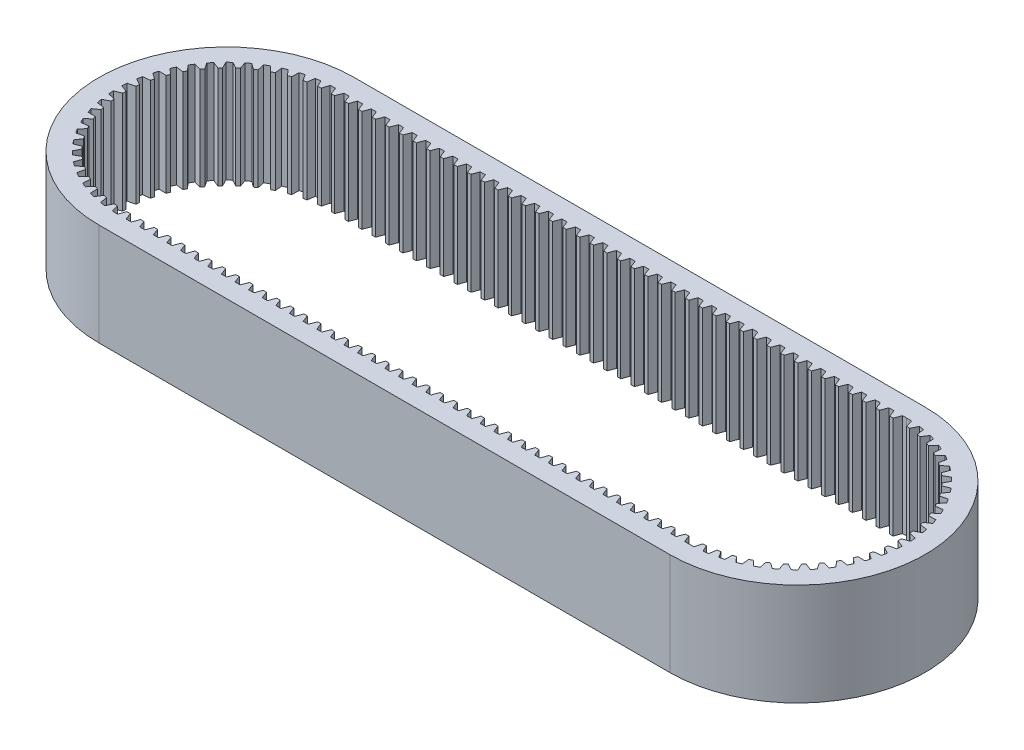
SolidWorks part; units mm, degrees
ref_plane "Front Plane" through (0, 0, 0) normal (0, 0, 1) x (1, 0, 0)
ref_plane "Top Plane" through (0, 0, 0) normal (0, 1, 0) x (1, 0, 0)
ref_plane "Right Plane" through (0, 0, 0) normal (1, 0, 0) x (0, 0, -1)
sketch "Sketch1" plane through (0, 0, 0) normal (0, 1, 0) x (1, 0, 0)
  line L0 (-16.765, 0) -> (16.765, 0) construction
  line L1 (-16.765, 6) -> (16.765, 6) construction
  line L2 (16.765, -6) -> (-16.765, -6) construction
  line L3 (16.765, -6.4) -> (-16.765, -6.4)
  line L4 (-16.765, 6.4) -> (16.765, 6.4)
  line L5 (16.765, -7.5) -> (-16.765, -7.5)
  line L6 (-16.765, 7.5) -> (16.765, 7.5)
  line L7 (-16.765, 6.4) -> (-16.615, 6)
  line L8 (-16.615, 6) -> (-16.415, 6)
  line L9 (-16.415, 6) -> (-16.265, 6.4)
  line L10 (-16.765, 6.4) -> (-16.265, 6.4)
  line L11 (-16.76, 6.3867) -> (-16.27, 6.3867) construction
  line L12 (-16.515, 6.3867) -> (-16.515, 6) construction
  arc A0 (-16.765, 6) -> (-16.765, -6) centre (-16.765, 0) ccw construction
  arc A1 (16.765, -6) -> (16.765, 6) centre (16.765, 0) ccw construction
  arc A2 (-16.765, 6.4) -> (-16.765, -6.4) centre (-16.765, 0) ccw
  arc A3 (16.765, -6.4) -> (16.765, 6.4) centre (16.765, 0) ccw
  arc A4 (-16.765, 7.5) -> (-16.765, -7.5) centre (-16.765, 0) ccw
  arc A5 (16.765, -7.5) -> (16.765, 7.5) centre (16.765, 0) ccw
  point P4 (0, 0)
  dimension "D2" = 12
  dimension "D3" = 12
  dimension "D1" = 33.53
  dimension "D6" = 33.53
  dimension "D7" = 0.5
  dimension "D8" = 0.2
  dimension "D9" = 0.0133
  dimension "D10" = 0.49
  dimension "D4" = 0.4
  dimension "D5" = 1.5
extrude "Boss-Extrude1" add sketch "Sketch1" along normal blind 6 contours L5 A5 L6 A4 A3 L3 A2 L4 region at (0, 0, 6.992)
extrude "Boss-Extrude2" add sketch "Sketch1<3>" along normal blind 6 contours L8 L9 L4 L7 region at (-16.515, 0, -6.2286)
sketch "Sketch1<3>" plane through (0, 0, 0) normal (0, 1, 0) x (1, 0, 0) same geometry as "Sketch1"
pattern_linear "LPattern1" count 42 spacing 0.8 along (1, 0, 0) of "Boss-Extrude2"
mirror "Mirror1" about plane through (0, 0, 0) normal (0, 0, 1) of "LPattern1", "Boss-Extrude2"
sketch "Sketch2" plane through (0, 0, 0) normal (0, -1, 0) x (1, 0, 0)
  line L0 (-17.0734, 6.3926) -> (-17.1883, 5.9859)
  line L1 (-17.1883, 5.9859) -> (-17.3876, 5.9685)
  line L2 (-17.3876, 5.9685) -> (-17.5714, 6.349)
  line L3 (-17.3228, 6.3756) -> (-17.2879, 5.9772) construction
  line L4 (-16.765, 0) -> (-17.3228, 6.3756) construction
  line L5 (-16.765, 0) -> (-23.165, 0) construction
  arc A0 (-16.765, 6.4) -> (-16.765, -6.4) centre (-16.765, 0) ccw construction
  arc A1 (-17.0734, 6.3926) -> (-17.5714, 6.349) centre (-16.765, 0) ccw
  arc A2 (-23.165, 0) -> (-16.765, -6.4) centre (-16.765, 0) ccw
  dimension "D1" = 0.25
  dimension "D2" = 0.2
  dimension "D3" = 0.25
  dimension "D4" = 85
  dimension "D5" = 0.4
extrude "Boss-Extrude3" add sketch "Sketch2" against normal blind 6 contours L0 A1 L2 L1 region at (-17.3078, 0, 6.2041)
pattern_circular "CirPattern1" count 25 over 170 about axis through (-16.765, 0, 0) along (0, 1, 0) of "Boss-Extrude3" reverse direction yes
mirror "Mirror2" about plane through (0, 0, 0) normal (1, 0, 0) of "Boss-Extrude3", "CirPattern1"
